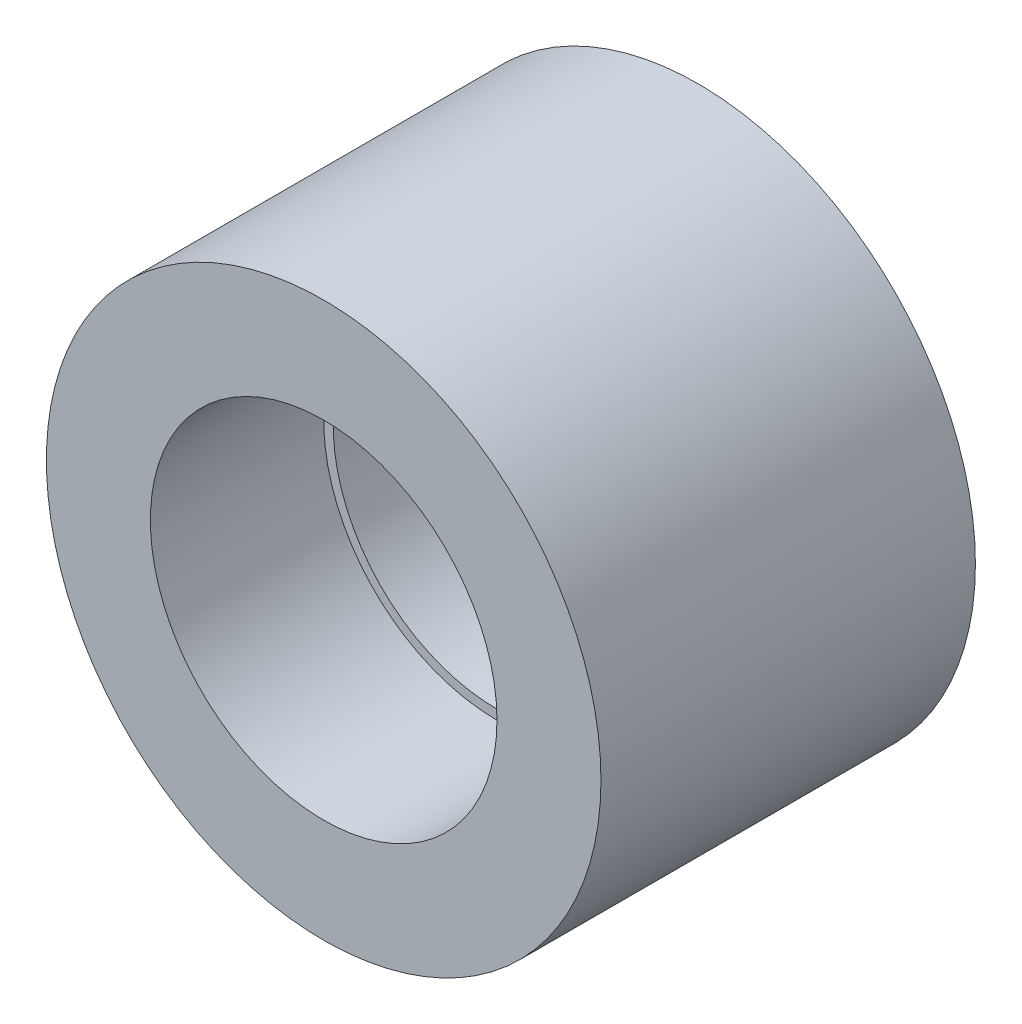
SolidWorks part; units mm, degrees
material "PLA"
ref_plane "Front Plane" through (0, 0, 0) normal (0, 0, 1) x (1, 0, 0)
ref_plane "Top Plane" through (0, 0, 0) normal (0, 1, 0) x (1, 0, 0)
ref_plane "Right Plane" through (0, 0, 0) normal (1, 0, 0) x (0, 0, -1)
sketch "Sketch1" plane through (0, 0, 0) normal (0, 0, 1) x (1, 0, 0)
  circle A0 centre (0, 0) radius 3
  circle A1 centre (0, 0) radius 3.175
  circle A2 centre (0, 0) radius 5.08
  dimension "D1" = 6
  dimension "D2" = 6.35
  dimension "D3" = 10.16
extrude "Boss-Extrude1" add sketch "Sketch1" along normal blind 3.175 contours A2 A1 region at (-4.9363, 0, 0)
extrude "Boss-Extrude2" add sketch "Sketch1<3>" against normal blind 3.6855 contours A1 A0 | A2 A1 region at (-3.0852, 0, 0) region at (-4.9363, 0, 0)
sketch "Sketch1<3>" plane through (0, 0, 0) normal (0, 0, 1) x (1, 0, 0) same geometry as "Sketch1"
